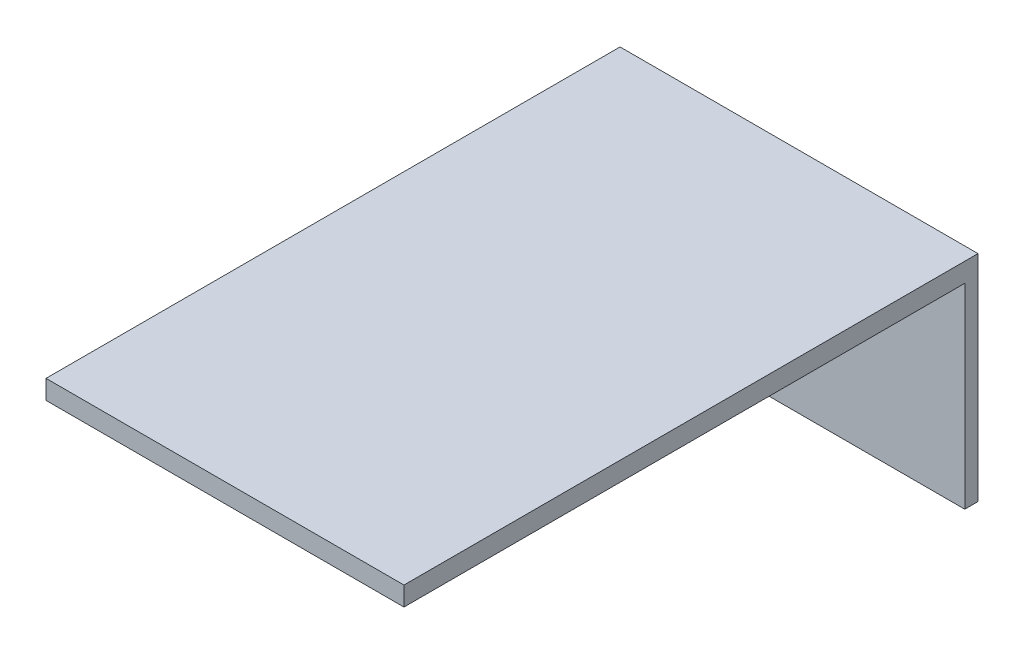
SolidWorks part; units mm, degrees
ref_plane "Ebene vorne" through (0, 0, 0) normal (0, 0, 1) x (1, 0, 0)
ref_plane "Ebene oben" through (0, 0, 0) normal (0, 1, 0) x (1, 0, 0)
ref_plane "Ebene rechts" through (0, 0, 0) normal (1, 0, 0) x (0, 0, -1)
sketch "Skizze1" plane through (0, 0, 0) normal (0, 0, 1) x (1, 0, 0)
  line L1 (-500, 300) -> (500, 300)
  line L2 (-500, 300) -> (-500, -300)
  line L3 (-500, -300) -> (500, -300)
  line L4 (500, 300) -> (500, -300)
  line L5 (-500, 300) -> (500, -300) construction
  line L6 (-500, -300) -> (500, 300) construction
  point P0 (0, 0)
  dimension "D1" = 600
  dimension "D2" = 1000
extrude "Aufsatz-Linear austragen1" add sketch "Skizze1" along normal blind 37
sketch "Skizze2" plane through (0, 0, 37) normal (0, 0, 1) x (1, 0, 0)
  line L0 (500, -300) -> (500, 300) construction
  line L1 (-500, 300) -> (500, 300)
  line L2 (-500, 300) -> (-500, 246.5988)
  line L3 (-500, 246.5988) -> (500, 246.5988)
  line L4 (500, 300) -> (500, 246.5988)
extrude "Aufsatz-Linear austragen2" add sketch "Skizze2" along normal blind 1566.7
